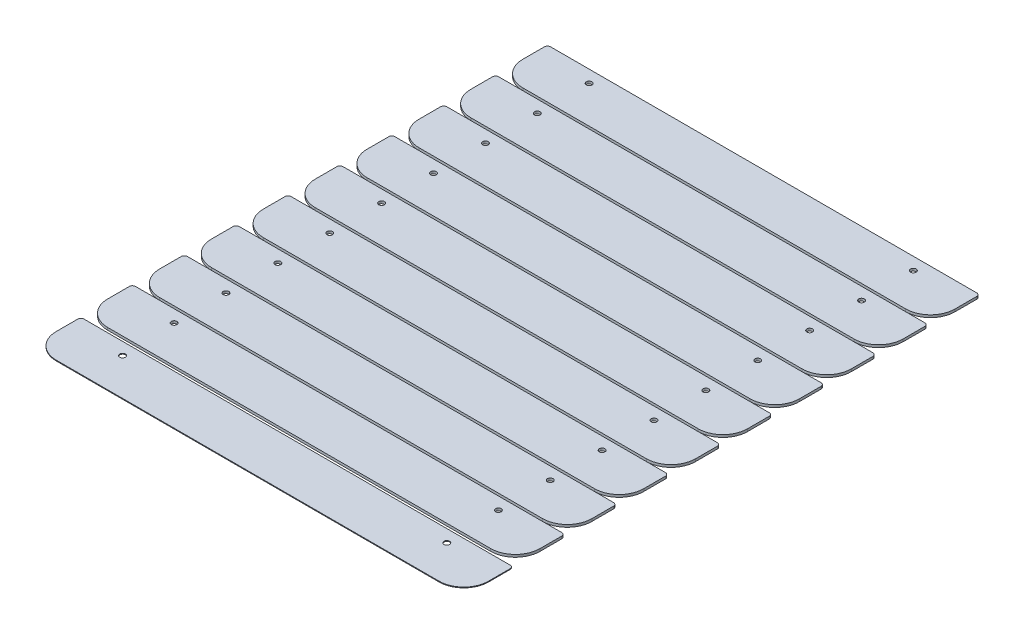
SolidWorks part; units mm, degrees
ref_plane "Front Plane" through (0, 0, 0) normal (0, 0, 1) x (1, 0, 0)
ref_plane "Top Plane" through (0, 0, 0) normal (0, 1, 0) x (1, 0, 0)
ref_plane "Right Plane" through (0, 0, 0) normal (1, 0, 0) x (0, 0, -1)
sketch "Sketch1" plane through (0, 0, 0) normal (0, 1, 0) x (1, 0, 0)
  line L1 (-222.25, -25.4) -> (222.25, -25.4)
  line L2 (-222.25, -25.4) -> (-222.25, 25.4)
  line L3 (-222.25, 25.4) -> (222.25, 25.4)
  line L4 (222.25, -25.4) -> (222.25, 25.4)
  line L5 (-222.25, -25.4) -> (222.25, 25.4) construction
  line L6 (-222.25, 25.4) -> (222.25, -25.4) construction
  point P0 (0, 0)
  dimension "D1" = 444.5
  dimension "D2" = 50.8
extrude "Boss-Extrude1" add sketch "Sketch1" along normal blind 0.7937
fillet "Fillet1" radius 25.4 2 edges at (222.25, 0.3969, 25.4) (-222.25, 0.3969, 25.4)
fillet "Fillet2" radius 3.175 2 edges at (-222.25, 0.3969, -25.4) (222.25, 0.3969, -25.4)
hole_wizard "#1 (0.228) Diameter Hole1" positions "Sketch2" profile "Sketch3" hole size "#1" standard "ANSI Inch" end condition through all
sketch "Sketch2" plane through (0, 0.7937, 0) normal (0, 1, 0) x (1, 0, 0)
  line L0 (-222.25, 12.7) -> (222.25, 12.7) construction
  line L1 (-222.25, 22.225) -> (-222.25, 0) construction
  line L2 (222.25, 0) -> (222.25, 22.225) construction
  line L4 (219.075, 25.4) -> (-219.075, 25.4) construction
  line L5 (0, 12.7) -> (0, 25.4) construction
  point P10 (-166.6875, 12.7)
  point P12 (166.6875, 12.7)
  dimension "D1" = 12.7
  dimension "D2" = 166.6875
  dimension "D3" = 166.6875
sketch "Sketch3" plane through (166.6875, 0.7937, -12.7) normal (1, 0, 0) x (0, 0, 1)
  line L0 (0, 0) -> (0, 0.7937)
  line L1 (0, 0.7937) -> (2.8956, 0.7937)
  line L2 (2.8956, 0.7937) -> (2.8956, 0)
  line L5 (2.8956, 0) -> (0, 0)
  line L11 (0, -6.35) -> (0, 107.95) construction
  dimension "Thru Hole Dia." = 5.7912
  dimension "Thru Hole Depth" = 0.7937
sketch "Sketch4" plane through (0, 0.7937, 0) normal (0, 1, 0) x (1, 0, 0)
  line L4 (222.25, 52.9984) -> (222.25, 75.2234)
  line L5 (-196.85, 27.5984) -> (196.85, 27.5984)
  line L6 (-222.25, 75.2234) -> (-222.25, 52.9984)
  line L7 (219.075, 78.3984) -> (-219.075, 78.3984)
  line L8 (222.25, 106.3384) -> (222.25, 128.5634)
  line L9 (-196.85, 80.9384) -> (196.85, 80.9384)
  line L10 (-222.25, 128.5634) -> (-222.25, 106.3384)
  line L11 (219.075, 131.7384) -> (-219.075, 131.7384)
  line L12 (222.25, 159.6784) -> (222.25, 181.9034)
  line L13 (-196.85, 134.2784) -> (196.85, 134.2784)
  line L14 (-222.25, 181.9034) -> (-222.25, 159.6784)
  line L15 (219.075, 185.0784) -> (-219.075, 185.0784)
  line L16 (222.25, 213.0184) -> (222.25, 235.2434)
  line L17 (-196.85, 187.6184) -> (196.85, 187.6184)
  line L18 (-222.25, 235.2434) -> (-222.25, 213.0184)
  line L19 (219.075, 238.4184) -> (-219.075, 238.4184)
  line L20 (222.25, 266.3584) -> (222.25, 288.5834)
  line L21 (-196.85, 240.9584) -> (196.85, 240.9584)
  line L22 (-222.25, 288.5834) -> (-222.25, 266.3584)
  line L23 (219.075, 291.7584) -> (-219.075, 291.7584)
  line L24 (222.25, 319.6984) -> (222.25, 341.9234)
  line L25 (-196.85, 294.2984) -> (196.85, 294.2984)
  line L26 (-222.25, 341.9234) -> (-222.25, 319.6984)
  line L27 (219.075, 345.0984) -> (-219.075, 345.0984)
  line L28 (222.25, 373.0384) -> (222.25, 395.2634)
  line L29 (-196.85, 347.6384) -> (196.85, 347.6384)
  line L30 (-222.25, 395.2634) -> (-222.25, 373.0384)
  line L31 (219.075, 398.4384) -> (-219.075, 398.4384)
  line L32 (222.25, 426.3784) -> (222.25, 448.6034)
  line L33 (-196.85, 400.9784) -> (196.85, 400.9784)
  line L34 (-222.25, 448.6034) -> (-222.25, 426.3784)
  line L35 (219.075, 451.7784) -> (-219.075, 451.7784)
  line L36 (222.25, 479.7184) -> (222.25, 501.9434)
  line L37 (-196.85, 454.3184) -> (196.85, 454.3184)
  line L38 (-222.25, 501.9434) -> (-222.25, 479.7184)
  line L39 (219.075, 505.1184) -> (-219.075, 505.1184)
  circle A6 centre (-166.6875, 65.6984) radius 2.8956
  circle A7 centre (166.6875, 65.6984) radius 2.8956
  arc A8 (222.25, 75.2234) -> (219.075, 78.3984) centre (219.075, 75.2234) ccw
  arc A9 (196.85, 27.5984) -> (222.25, 52.9984) centre (196.85, 52.9984) ccw
  arc A10 (-222.25, 52.9984) -> (-196.85, 27.5984) centre (-196.85, 52.9984) ccw
  arc A11 (-219.075, 78.3984) -> (-222.25, 75.2234) centre (-219.075, 75.2234) ccw
  circle A12 centre (-166.6875, 119.0384) radius 2.8956
  circle A13 centre (166.6875, 119.0384) radius 2.8956
  arc A14 (222.25, 128.5634) -> (219.075, 131.7384) centre (219.075, 128.5634) ccw
  arc A15 (196.85, 80.9384) -> (222.25, 106.3384) centre (196.85, 106.3384) ccw
  arc A16 (-222.25, 106.3384) -> (-196.85, 80.9384) centre (-196.85, 106.3384) ccw
  arc A17 (-219.075, 131.7384) -> (-222.25, 128.5634) centre (-219.075, 128.5634) ccw
  circle A18 centre (-166.6875, 172.3784) radius 2.8956
  circle A19 centre (166.6875, 172.3784) radius 2.8956
  arc A20 (222.25, 181.9034) -> (219.075, 185.0784) centre (219.075, 181.9034) ccw
  arc A21 (196.85, 134.2784) -> (222.25, 159.6784) centre (196.85, 159.6784) ccw
  arc A22 (-222.25, 159.6784) -> (-196.85, 134.2784) centre (-196.85, 159.6784) ccw
  arc A23 (-219.075, 185.0784) -> (-222.25, 181.9034) centre (-219.075, 181.9034) ccw
  circle A24 centre (-166.6875, 225.7184) radius 2.8956
  circle A25 centre (166.6875, 225.7184) radius 2.8956
  arc A26 (222.25, 235.2434) -> (219.075, 238.4184) centre (219.075, 235.2434) ccw
  arc A27 (196.85, 187.6184) -> (222.25, 213.0184) centre (196.85, 213.0184) ccw
  arc A28 (-222.25, 213.0184) -> (-196.85, 187.6184) centre (-196.85, 213.0184) ccw
  arc A29 (-219.075, 238.4184) -> (-222.25, 235.2434) centre (-219.075, 235.2434) ccw
  circle A30 centre (-166.6875, 279.0584) radius 2.8956
  circle A31 centre (166.6875, 279.0584) radius 2.8956
  arc A32 (222.25, 288.5834) -> (219.075, 291.7584) centre (219.075, 288.5834) ccw
  arc A33 (196.85, 240.9584) -> (222.25, 266.3584) centre (196.85, 266.3584) ccw
  arc A34 (-222.25, 266.3584) -> (-196.85, 240.9584) centre (-196.85, 266.3584) ccw
  arc A35 (-219.075, 291.7584) -> (-222.25, 288.5834) centre (-219.075, 288.5834) ccw
  circle A36 centre (-166.6875, 332.3984) radius 2.8956
  circle A37 centre (166.6875, 332.3984) radius 2.8956
  arc A38 (222.25, 341.9234) -> (219.075, 345.0984) centre (219.075, 341.9234) ccw
  arc A39 (196.85, 294.2984) -> (222.25, 319.6984) centre (196.85, 319.6984) ccw
  arc A40 (-222.25, 319.6984) -> (-196.85, 294.2984) centre (-196.85, 319.6984) ccw
  arc A41 (-219.075, 345.0984) -> (-222.25, 341.9234) centre (-219.075, 341.9234) ccw
  circle A42 centre (-166.6875, 385.7384) radius 2.8956
  circle A43 centre (166.6875, 385.7384) radius 2.8956
  arc A44 (222.25, 395.2634) -> (219.075, 398.4384) centre (219.075, 395.2634) ccw
  arc A45 (196.85, 347.6384) -> (222.25, 373.0384) centre (196.85, 373.0384) ccw
  arc A46 (-222.25, 373.0384) -> (-196.85, 347.6384) centre (-196.85, 373.0384) ccw
  arc A47 (-219.075, 398.4384) -> (-222.25, 395.2634) centre (-219.075, 395.2634) ccw
  circle A48 centre (-166.6875, 439.0784) radius 2.8956
  circle A49 centre (166.6875, 439.0784) radius 2.8956
  arc A50 (222.25, 448.6034) -> (219.075, 451.7784) centre (219.075, 448.6034) ccw
  arc A51 (196.85, 400.9784) -> (222.25, 426.3784) centre (196.85, 426.3784) ccw
  arc A52 (-222.25, 426.3784) -> (-196.85, 400.9784) centre (-196.85, 426.3784) ccw
  arc A53 (-219.075, 451.7784) -> (-222.25, 448.6034) centre (-219.075, 448.6034) ccw
  circle A54 centre (-166.6875, 492.4184) radius 2.8956
  circle A55 centre (166.6875, 492.4184) radius 2.8956
  arc A56 (222.25, 501.9434) -> (219.075, 505.1184) centre (219.075, 501.9434) ccw
  arc A57 (196.85, 454.3184) -> (222.25, 479.7184) centre (196.85, 479.7184) ccw
  arc A58 (-222.25, 479.7184) -> (-196.85, 454.3184) centre (-196.85, 479.7184) ccw
  arc A59 (-219.075, 505.1184) -> (-222.25, 501.9434) centre (-219.075, 501.9434) ccw
  dimension "D1" = 9
extrude "Boss-Extrude2" add sketch "Sketch4" along normal blind 2.54 separate body
